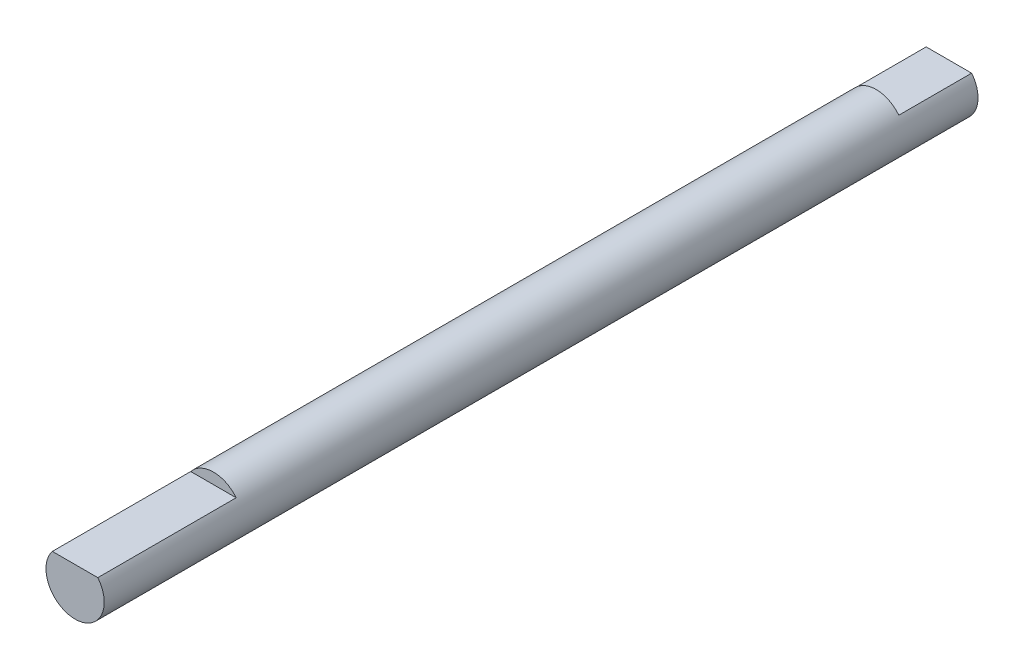
SolidWorks part; units mm, degrees
ref_plane "Front Plane" through (0, 0, 0) normal (0, 0, 1) x (1, 0, 0)
ref_plane "Top Plane" through (0, 0, 0) normal (0, 1, 0) x (1, 0, 0)
ref_plane "Right Plane" through (0, 0, 0) normal (1, 0, 0) x (0, 0, -1)
sketch "Sketch2" plane through (0, 0, 0) normal (0, 0, 1) x (1, 0, 0)
  circle A0 centre (0, 0) radius 4
  dimension "D1" = 8
extrude "Boss-Extrude1" add sketch "Sketch2" along normal blind 120
sketch "Sketch3" plane through (0, 0, 0) normal (0, 0, 1) x (1, 0, 0)
  line L0 (-3.1225, 2.5) -> (3.1225, 2.5)
  circle A0 centre (0, 0) radius 4 construction
  arc A1 (3.1225, 2.5) -> (-3.1225, 2.5) centre (0, 0) ccw
  dimension "D1" = 2.5
extrude "Cut-Extrude1" cut sketch "Sketch3" along normal blind 10
extrude "Cut-Extrude2" cut sketch "Sketch3<2>" against normal blind 19 from surface starting at face at (4, 0, 120)
sketch "Sketch3<2>" plane through (0, 0, 0) normal (0, 0, 1) x (1, 0, 0) same geometry as "Sketch3"
